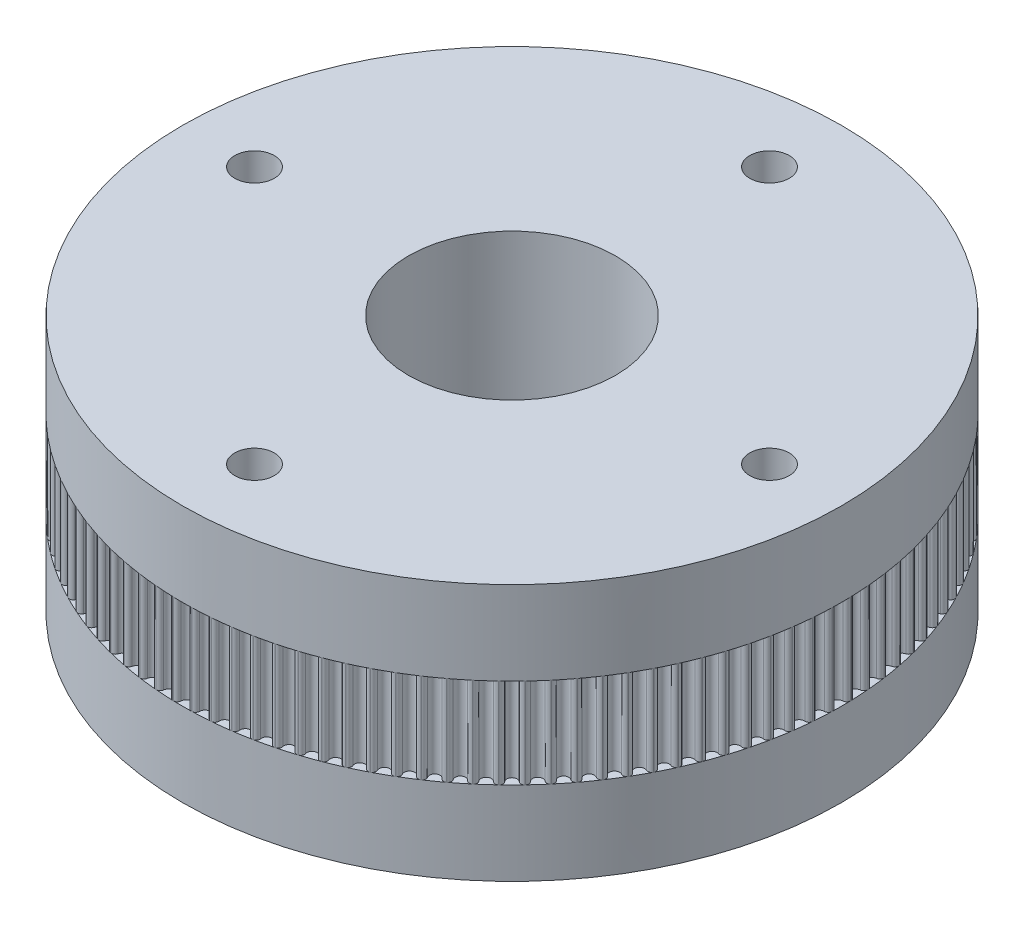
SolidWorks part; units mm, degrees
ref_plane "Front plan" through (0, 0, 0) normal (0, 0, 1) x (1, 0, 0)
ref_plane "Top plan" through (0, 0, 0) normal (0, 1, 0) x (1, 0, 0)
ref_plane "Right plan" through (0, 0, 0) normal (1, 0, 0) x (0, 0, -1)
sketch "Skica2" plane through (0, 0, 0) normal (0, 0, 1) x (1, 0, 0)
  line L1 (11, 4.775) -> (11, -4.775)
  line L3 (0, -9) -> (0, 9) construction
  line L7 (36, 3.775) -> (35, 3.775)
  line L8 (35, 3.775) -> (35, -3.775)
  line L9 (36, 3.775) -> (36, 4.775)
  line L12 (36, -4.775) -> (8.107, -4.775)
  line L13 (36, 4.775) -> (12.5, 4.775)
  line L14 (36, -4.775) -> (36, -3.775)
  line L15 (35, -3.775) -> (36, -3.775)
  line L17 (12.5, 4.775) -> (11, 4.775)
  line L18 (8.107, -4.775) -> (11, -4.775)
  point P3 (11, 0)
  point P7 (0, 0)
  dimension "D3" = 70
  dimension "D1" = 22
  dimension "D2" = 9.55
  dimension "D4" = 1
  dimension "D5" = 1
revolve "Revolute" add sketch "Skica2" angle 360 about L3
sketch "Sketch2" plane through (0, 3.775, 0) normal (0, -1, 0) x (1, 0, 0)
  line L0 (0, 0) -> (0, 34.6075) construction
  line L1 (0, 0) -> (11.8019, 32.9502) construction
  line L3 (0, 0) -> (-2.5216, 34.909) construction
  circle A1 centre (0, 0) radius 34.0575 construction
  circle A2 centre (0, 0) radius 34.6 construction
  arc A3 (-0.5499, 34.5956) -> (0.5499, 34.5956) centre (0, 34.6075) ccw
  arc A7 (-0.9608, 34.9868) -> (-2.5216, 34.909) centre (0, 0) ccw
  arc A8 (0, 36.241) -> (2.5216, 34.909) centre (0.9503, 34.9871) cw
  circle A9 centre (0, 0) radius 35 construction
  arc A10 (0.9608, 34.9868) -> (2.5216, 34.909) centre (0, 0) cw
  arc A11 (0.9608, 34.9868) -> (0.5499, 34.5956) centre (0.9498, 34.587) ccw
  arc A12 (0, 36.241) -> (-2.5216, 34.909) centre (-0.9503, 34.9871) ccw
  arc A13 (-0.9608, 34.9868) -> (-0.5499, 34.5956) centre (-0.9498, 34.587) cw
  dimension "D2" = 0.8
  dimension "D4" = 0.55
  dimension "D6" = 70
  dimension "D3" = 1.5733
  dimension "D1" = 0.4
extrude "Cut-Extrude3" cut sketch "Sketch2" along normal mid plane 50
pattern_circular "CirPattern1" count 112 over 360 about axis through (0, 0, 0) along (0, 1, 0) of "Cut-Extrude3"
sketch "Sketch4" plane through (0, -4.775, 0) normal (0, -1, 0) x (1, 0, 0)
  circle A0 centre (0, 0) radius 20.125
  circle A1 centre (0, 0) radius 7.25
  dimension "D1" = 40.25
  dimension "D2" = 14.5
extrude "Cut-Extrude4" [suppressed] cut sketch "Sketch4" against normal blind 2
ref_plane "Plane1" through (0, 1.575, 0) normal (0, -1, 0) x (-1, 0, 0)
mirror "Mirror1" [suppressed] about plane through (0, 0, 0) normal (0, 1, 0)
sketch "Sketch7" plane through (0, -4.775, 0) normal (0, -1, 0) x (1, 0, 0)
  circle A0 centre (-27.35, 0) radius 2.1
  point P2 (0, 0)
  point P4 (0, 0)
  point P5 (-27.35, 0)
  dimension "D1" = 27.35
  dimension "D2" = 4.2
extrude "Cut-Extrude5" cut sketch "Sketch7" against normal through all
pattern_circular "CirPattern2" count 4 over 270 about axis through (0, 0, 0) along (0, 1, 0) of "Cut-Extrude5"
sketch "Sketch8" plane through (0, -4.775, 0) normal (0, -1, 0) x (1, 0, 0)
  circle A0 centre (0, 0) radius 35
  circle A1 centre (-27.35, 0) radius 2.1
  circle A2 centre (0, 27.35) radius 2.1
  circle A3 centre (27.35, 0) radius 2.1
  circle A4 centre (0, -27.35) radius 2.1
  circle A6 centre (0, 0) radius 11
  circle A8 centre (0, 0) radius 11 construction
  circle A9 centre (-27.35, 0) radius 2.1 construction
  circle A10 centre (0, -27.35) radius 2.1 construction
extrude "Boss-Extrude1" add sketch "Sketch8" along normal blind 8.875
mirror "Mirror2" about plane through (0, 0, 0) normal (0, 1, 0) of "Boss-Extrude1"
equation "\"`\"=2"
equation "\"D6@Sketch2\"= \"D3@Skica2\""
